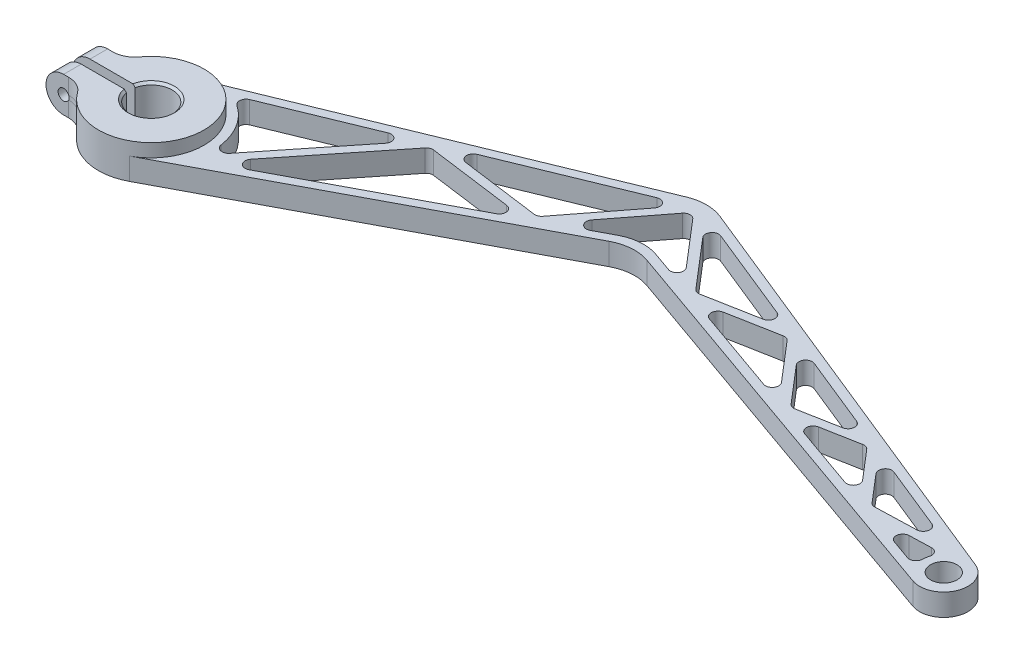
SolidWorks part; units mm, degrees
material "6061-T6 (SS)"
ref_plane "Front Plane" through (0, 0, 0) normal (0, 0, 1) x (1, 0, 0)
ref_plane "Top Plane" through (0, 0, 0) normal (0, 1, 0) x (1, 0, 0)
ref_plane "Right Plane" through (0, 0, 0) normal (1, 0, 0) x (0, 0, -1)
sketch "Sketch1" plane through (0, 0, 0) normal (0, 1, 0) x (1, 0, 0)
  line L0 (0, 0) -> (-42.5984, 0) construction
  line L1 (-18.9087, -5) -> (-18.9087, -1)
  line L2 (-18.9087, 5) -> (-10.9087, 5)
  line L3 (-18.9087, -5) -> (-10.9087, -5)
  line L4 (-18.9087, 1) -> (-4.6487, 1)
  line L5 (-18.9087, -1) -> (-4.6487, -1)
  line L6 (-18.9087, 1) -> (-18.9087, 5)
  arc A0 (-4.6487, -1) -> (-4.6487, 1) centre (0, 0) ccw
  arc A1 (-10.9087, -5) -> (-10.9087, 5) centre (0, 0) ccw
  point P8 (-42.5984, 0)
  dimension "D1" = 4.755
  dimension "D5" = 12
  dimension "D2" = 4
  dimension "D3" = 1
  dimension "D4" = 8
extrude "Boss-Extrude1" add sketch "Sketch1" along normal blind 8
sketch "Sketch2" plane through (0, 0, 0) normal (0, 1, 0) x (1, 0, 0)
  line L0 (0, 0) -> (180, 0) construction
  line L1 (182.0653, 5.0975) -> (80.7418, 46.1505)
  line L2 (80.7418, 46.1505) -> (-4.5608, 11.0995)
  line L3 (178.1718, -5.1873) -> (80.7418, 29.1505)
  line L4 (80.7418, 29.1505) -> (5.6128, -10.6065)
  line L5 (80.7418, 46.1505) -> (80.7418, 29.1505) construction
  line L6 (0, 0) -> (80.7418, 37.6505) construction
  line L7 (80.7418, 37.6505) -> (180, 0) construction
  arc A0 (-10.9087, -5) -> (-10.9087, 5) centre (0, 0) ccw construction
  arc A1 (5.6128, -10.6065) -> (-4.5608, 11.0995) centre (0, 0) ccw
  circle A2 centre (180, 0) radius 3
  arc A3 (178.1718, -5.1873) -> (182.0653, 5.0975) centre (180, 0) ccw
  dimension "D2" = 6
  dimension "D3" = 5.5
  dimension "D1" = 180
  dimension "D4" = 85
  dimension "D5" = 25
  dimension "D6" = 17
extrude "Boss-Extrude2" add sketch "Sketch2" along normal blind 5
sketch "Sketch3" plane through (0, 0, -5) normal (0, 0, -1) x (-1, 0, 0)
  line L0 (18.9087, 4) -> (10.9087, 4) construction
  line L1 (18.9087, 8) -> (18.9087, 0) construction
  line L2 (10.9087, 8) -> (10.9087, 0) construction
  line L3 (14.9087, 8) -> (14.9087, 0) construction
  line L4 (10.9087, 8) -> (18.9087, 8) construction
  line L5 (10.9087, 0) -> (18.9087, 0) construction
  point P12 (14.9087, 4)
hole_wizard "CBORE for M3 SHCS1" positions "Sketch8" profile "Sketch9" counterbore size "M3" standard "ANSI Metric"
sketch "Sketch8" plane through (0, 0, -5) normal (0, 0, -1) x (-1, 0, 0)
  point P0 (14.9087, 4)
sketch "Sketch9" plane through (-14.9087, 4, -5) normal (1, 0, 0) x (0, 1, 0)
  line L0 (0, 0) -> (0, 5.9614)
  line L1 (0, 5.9614) -> (1.6, 5)
  line L2 (1.6, 5) -> (1.6, 3)
  line L3 (1.6, 3) -> (3.25, 3)
  line L4 (3.25, 3) -> (3.25, 0)
  line L5 (3.25, 0) -> (0, 0)
  line L10 (0, 5.9614) -> (-1.6, 5) construction
  line L11 (0, -6.35) -> (0, 107.95) construction
  dimension "Hole Dia." = 3.2
  dimension "Hole Depth" = 5
  dimension "C'Bore Dia." = 6.5
  dimension "C'Bore Depth" = 3
  dimension "Drill Angle" = 118
sketch "Sketch10" plane through (0, 0, 1) normal (0, 0, -1) x (-1, 0, 0)
  point P0 (14.9087, 4)
hole_wizard "M3x0.5 Tapped Hole1" positions "Sketch12" profile "Sketch11" tap size "M3x0.5" standard "ANSI Metric" end condition through all
sketch "Sketch12" plane through (0, 0, 1) normal (0, 0, -1) x (-1, 0, 0)
  point P0 (14.9087, 4)
sketch "Sketch11" plane through (-14.9087, 4, 1) normal (1, 0, 0) x (0, 1, 0)
  line L0 (0, 0) -> (0, 11)
  line L1 (0, 11) -> (1.25, 11)
  line L2 (1.25, 11) -> (1.25, 0)
  line L5 (1.25, 0) -> (0, 0)
  line L11 (0, -6.35) -> (0, 107.95) construction
  dimension "Thru Tap Drill Dia." = 2.5
  dimension "Thru Tap Drill Depth" = 11
cosmetic thread "Hole Thread1" parameters "D2"=3
fillet "Fillet1" radius 4 4 edges at (-18.9087, 8, 3) (-18.9087, 0, 3) (-18.9087, 0, -3) (-18.9087, 8, -3)
fillet "Fillet2" radius 5 2 edges at (-10.9087, 4, 5) (-10.9087, 4, -5)
chamfer "Chamfer1" distance 0.5 angle 45 2 edges at (4.755, 0, 0) (4.755, 8, 0)
sketch "Sketch14" plane through (0, 5, 0) normal (0, 1, 0) x (1, 0, 0)
  line L0 (180, 0) -> (0, 0) construction
sketch "Sketch15" plane through (0, 5, 0) normal (0, 1, 0) x (1, 0, 0)
  line L4 (80.5806, 31.328) -> (80.7472, 43.9905) construction
  line L5 (12.6767, 5.9415) -> (80.6639, 37.6592) construction
  line L6 (80.6639, 37.6592) -> (180, 0) construction
  line L8 (181.3143, 3.2439) -> (80.7472, 43.9905)
  line L9 (80.7472, 43.9905) -> (5.262, 12.9735)
  line L10 (13.3374, -4.2559) -> (80.5806, 31.328)
  line L11 (80.5806, 31.328) -> (178.8366, -3.301)
  line L12 (178.0049, 4.5847) -> (80.7472, 43.9905)
  line L13 (80.7472, 43.9905) -> (5.262, 12.9735)
  line L14 (13.3374, -4.2559) -> (80.5806, 31.328)
  line L15 (80.5806, 31.328) -> (175.4689, -2.1141)
  circle A2 centre (180, 0) radius 5
  arc A3 (178.0049, 4.5847) -> (175.4689, -2.1141) centre (180, 0) ccw
  arc A4 (178.8366, -3.301) -> (181.3143, 3.2439) centre (180, 0) ccw
  arc A5 (13.3374, -4.2559) -> (5.262, 12.9735) centre (0, 0) ccw
  arc A7 (13.3374, -4.2559) -> (5.262, 12.9735) centre (0, 0) ccw
  dimension "D1" = 2
  dimension "D2" = 2
extrude "Cut-Extrude1" cut sketch "Sketch15" against normal through all contours L13 A7 L14 L15 A3 L12
sketch "Sketch17" plane through (0, 0, 0) normal (0, 1, 0) x (1, 0, 0)
  line L0 (13.3374, -4.2559) -> (37.7293, 26.3143)
  line L1 (80.7472, 43.9905) -> (5.262, 12.9735) construction
  line L2 (37.7293, 26.3143) -> (64.3409, 22.7342)
  line L3 (13.3374, -4.2559) -> (80.5806, 31.328) construction
  line L4 (64.3409, 22.7342) -> (80.7472, 43.9905)
  line L5 (80.7472, 43.9905) -> (96.3584, 25.7673)
  line L6 (96.3584, 25.7673) -> (116.4545, 29.523)
  line L7 (178.0049, 4.5847) -> (80.7472, 43.9905) construction
  line L8 (146.8767, 17.1969) -> (158.2086, 3.9691)
  line L9 (80.5806, 31.328) -> (175.4689, -2.1141) construction
  line L10 (116.4545, 29.523) -> (129.7551, 13.9971)
  line L11 (129.7551, 13.9971) -> (146.8767, 17.1969)
  line L12 (80.5806, 31.328) -> (80.7472, 43.9905) construction
  line L13 (80.6639, 37.6592) -> (12.6767, 5.9415) construction
  line L14 (80.6639, 37.6592) -> (175.3239, 1.7703) construction
  line L15 (116.4545, 29.523) -> (113.0568, 19.8822) construction
  line L16 (146.8767, 17.1969) -> (143.9818, 8.9831) construction
  line L17 (64.3409, 22.7342) -> (59.2382, 35.1524) construction
  line L18 (37.7293, 26.3143) -> (45.0312, 12.5159) construction
  line L19 (158.2086, 3.9691) -> (178.0049, 4.5847)
  arc A0 (13.3374, -4.2559) -> (5.262, 12.9735) centre (0, 0) ccw construction
  arc A1 (178.0049, 4.5847) -> (175.4689, -2.1141) centre (180, 0) ccw construction
  dimension "D1" = 60
  dimension "D2" = 60
  dimension "D3" = 120
  dimension "D4" = 60
  dimension "D5" = 60
  dimension "D6" = 60
  dimension "D7" = 60
extrude "Extrude-Thin2" add sketch "Sketch17" along normal up to surface (5 mm away) thin up to face at (89.2275, 5, -14.7707) thin type mid plane wall 2
fillet "Fillet6" radius 10 3 edges at (80.7418, 2.5, -46.1505) (80.7418, 2.5, -29.1505) (80.5806, 2.5, -31.328)
fillet "Fillet8" radius 1.5 30 edges at (156.3223, 2.5, -4.6339) (146.4929, 2.5, -16.1078) (131.6414, 2.5, -13.3323) (116.0707, 2.5, -28.4339) (98.2447, 2.5, -25.1025) (127.8688, 2.5, -14.6619) (94.4722, 2.5, -26.4321) (80.7876, 2.5, -42.4062) (66.4763, 2.5, -23.8642) (15.5517, 2.5, 3.0842) (62.8206, 2.5, -21.9297) (5.262, 2.5, -12.9735) (13.856, 2.5, 2.0026) (35.826, 2.5, -25.5323) (39.5792, 2.5, -27.0745) (63.902, 2.5, -23.8023) (78.8972, 2.5, -43.2303) (82.7639, 2.5, -43.1733) (96.7423, 2.5, -26.8563) (114.7363, 2.5, -30.2192) (118.4713, 2.5, -28.7058) (130.1389, 2.5, -15.0861) (145.1584, 2.5, -17.8931) (148.8935, 2.5, -16.3797) (158.6563, 2.5, -4.9835) (175.7116, 2.5, -5.5139) (160.8172, 2.5, -3.0497) (175.4689, 2.5, 2.1141) (176.4653, 2.5, -3.5364) (38.1575, 2.5, -25.2477)
